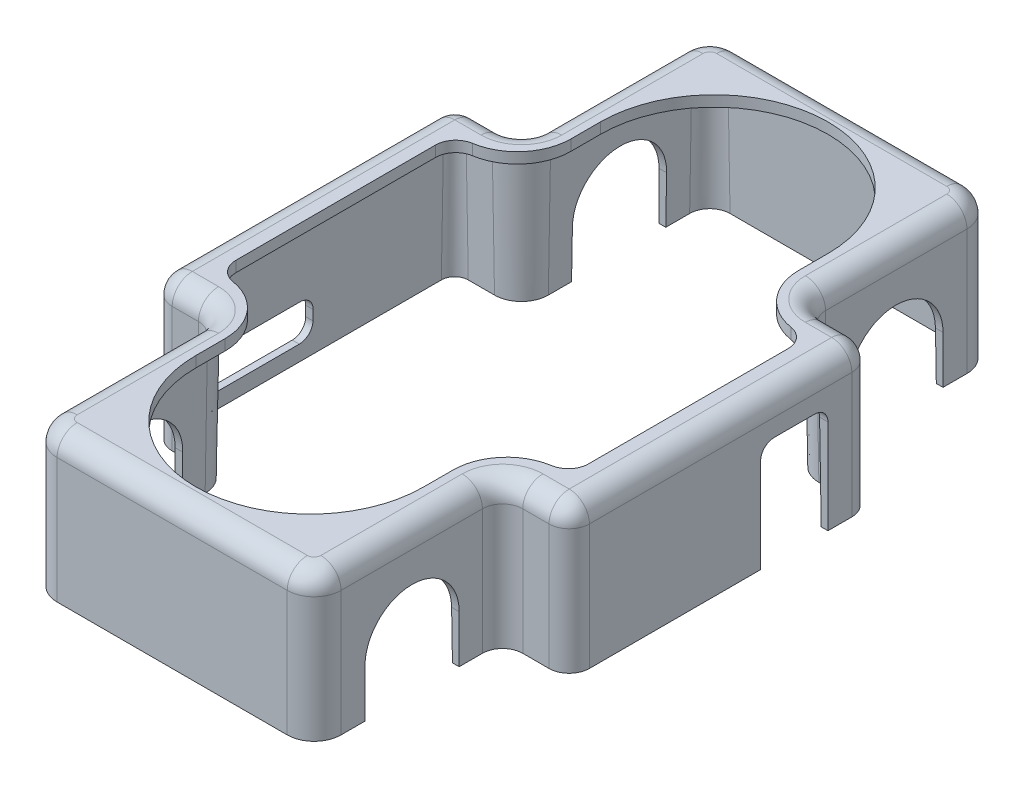
SolidWorks part; units mm, degrees
ref_plane "Front Plane" through (0, 0, 0) normal (0, 0, 1) x (1, 0, 0)
ref_plane "Top Plane" through (0, 0, 0) normal (0, 1, 0) x (1, 0, 0)
ref_plane "Right Plane" through (0, 0, 0) normal (1, 0, 0) x (0, 0, -1)
sketch "Sketch1" plane through (0, 0, 0) normal (0, 1, 0) x (1, 0, 0)
  line L1 (-155, -252.5) -> (155, -252.5)
  line L2 (-155, -252.5) -> (-155, 252.5)
  line L3 (-155, 252.5) -> (155, 252.5)
  line L4 (155, -252.5) -> (155, 252.5)
  line L5 (-155, -252.5) -> (155, 252.5) construction
  line L6 (-155, 252.5) -> (155, -252.5) construction
  point P0 (0, 0)
  dimension "D1" = 310
  dimension "D2" = 505
extrude "Boss-Extrude1" add sketch "Sketch1" along normal blind 108
sketch "Sketch2" plane through (0, 0, 0) normal (0, -1, 0) x (-1, 0, 0)
  line L0 (155, -252.5) -> (-155, -252.5) construction
  line L1 (180.5, -252.5) -> (105.5, -252.5)
  line L2 (180.5, -252.5) -> (180.5, -112.5)
  line L3 (180.5, -112.5) -> (105.5, -112.5)
  line L4 (105.5, -252.5) -> (105.5, -112.5)
  line L5 (0, 0) -> (-155, 0) construction
  line L6 (-155, -252.5) -> (-155, 252.5) construction
  line L7 (0, 0) -> (0, -252.5) construction
  line L8 (-105.5, -252.5) -> (-105.5, -112.5)
  line L9 (-180.5, -112.5) -> (-105.5, -112.5)
  line L10 (-180.5, -252.5) -> (-180.5, -112.5)
  line L11 (-180.5, -252.5) -> (-105.5, -252.5)
  line L12 (-180.5, 252.5) -> (-105.5, 252.5)
  line L13 (-180.5, 252.5) -> (-180.5, 112.5)
  line L14 (-180.5, 112.5) -> (-105.5, 112.5)
  line L15 (-105.5, 252.5) -> (-105.5, 112.5)
  line L16 (105.5, 252.5) -> (105.5, 112.5)
  line L17 (180.5, 112.5) -> (105.5, 112.5)
  line L18 (180.5, 252.5) -> (180.5, 112.5)
  line L19 (180.5, 252.5) -> (105.5, 252.5)
  dimension "D1" = 140
  dimension "D2" = 75
extrude "Cut-Extrude1" cut sketch "Sketch2" against normal through all
fillet "Fillet1" radius 15 4 edges at (105.5, 54, 112.5) (-105.5, 54, 112.5) (105.5, 54, -112.5) (-105.5, 54, -112.5)
fillet "Fillet3" radius 20 4 edges at (105.5, 54, 252.5) (-105.5, 54, 252.5) (105.5, 54, -252.5) (-105.5, 54, -252.5)
fillet "Fillet4" radius 15 20 edges at (-109.8934, 108, 116.8934) (-105.5, 108, 180) (-99.6421, 108, 246.6421) (0, 108, 252.5) (99.6421, 108, 246.6421) (109.8934, 108, 116.8934) (-109.8934, 108, -116.8934) (-105.5, 108, -180) (-99.6421, 108, -246.6421) (0, 108, -252.5) (99.6421, 108, -246.6421) (105.5, 108, -180) (109.8934, 108, -116.8934) (105.5, 108, 180) (155, 108, 0) (-155, 108, 0) (-137.75, 108, 112.5) (137.75, 108, 112.5) (-137.75, 108, -112.5) (137.75, 108, -112.5)
fillet "Fillet5" radius 15 8 edges at (-150.6066, 103.6066, 108.1066) (-150.6066, 103.6066, -108.1066) (150.6066, 103.6066, -108.1066) (150.6066, 103.6066, 108.1066) (-155, 46.5, 112.5) (-155, 46.5, -112.5) (155, 46.5, -112.5) (155, 46.5, 112.5)
ref_plane "Plane1" through (0, -10, 0) normal (0, -1, 0) x (-1, 0, 0)
sketch "Sketch16" plane through (-105.5, 0, 0) normal (-1, 0, 0) x (0, 0, 1)
  line L0 (-179.75, 35.4494) -> (-179.75, -45.4494) construction
  line L1 (-144.75, 35.4494) -> (-144.75, -45.4494)
  line L2 (-214.75, 35.4494) -> (-214.75, -45.4494)
  line L3 (0, 0) -> (0, -82.7143) construction
  line L4 (179.75, 35.4494) -> (179.75, -45.4494) construction
  line L5 (144.75, 35.4494) -> (144.75, -45.4494)
  line L6 (214.75, 35.4494) -> (214.75, -45.4494)
  line L7 (-232.5, 0) -> (-127.5, 0) construction
  arc A0 (-144.75, 35.4494) -> (-214.75, 35.4494) centre (-179.75, 35.4494) ccw
  arc A1 (-214.75, -45.4494) -> (-144.75, -45.4494) centre (-179.75, -45.4494) ccw
  arc A2 (144.75, 35.4494) -> (214.75, 35.4494) centre (179.75, 35.4494) cw
  arc A3 (214.75, -45.4494) -> (144.75, -45.4494) centre (179.75, -45.4494) cw
  point P2 (-179.75, -5)
  point P11 (179.75, -5)
  dimension "D1" = 35
  dimension "D2" = 5
extrude "Cut-Extrude2" cut sketch "Sketch16" against normal through all
sketch "Sketch17" plane through (0, 0, 0) normal (0, -1, 0) x (-1, 0, 0)
  line L413 (-100.5, -214.75) -> (-100.5, -232.5)
  line L414 (-100.5, -144.75) -> (-100.5, -214.75)
  line L415 (-100.5, -127.5) -> (-100.5, -144.75)
  line L416 (-140, -107.5) -> (-120.5, -107.5)
  line L417 (-150, 97.5) -> (-150, -97.5)
  line L418 (-120.5, 107.5) -> (-140, 107.5)
  line L419 (-100.5, 144.75) -> (-100.5, 127.5)
  line L420 (-100.5, 214.75) -> (-100.5, 144.75)
  line L421 (-100.5, 232.5) -> (-100.5, 214.75)
  line L422 (85.5, 247.5) -> (-85.5, 247.5)
  line L423 (100.5, 214.75) -> (100.5, 232.5)
  line L424 (100.5, 144.75) -> (100.5, 214.75)
  line L425 (100.5, 127.5) -> (100.5, 144.75)
  line L426 (140, 107.5) -> (120.5, 107.5)
  line L427 (150, -97.5) -> (150, 97.5)
  line L428 (120.5, -107.5) -> (140, -107.5)
  line L429 (100.5, -144.75) -> (100.5, -127.5)
  line L430 (100.5, -214.75) -> (100.5, -144.75)
  line L431 (100.5, -232.5) -> (100.5, -214.75)
  line L432 (-85.5, -247.5) -> (85.5, -247.5)
  line L433 (-100.5, -214.75) -> (-100.5, -232.5)
  line L434 (-100.5, -144.75) -> (-100.5, -214.75)
  line L435 (-100.5, -127.5) -> (-100.5, -144.75)
  line L436 (-140, -107.5) -> (-120.5, -107.5)
  line L437 (-150, 97.5) -> (-150, -97.5)
  line L438 (-120.5, 107.5) -> (-140, 107.5)
  line L439 (-100.5, 144.75) -> (-100.5, 127.5)
  line L440 (-100.5, 214.75) -> (-100.5, 144.75)
  line L441 (-100.5, 232.5) -> (-100.5, 214.75)
  line L442 (85.5, 247.5) -> (-85.5, 247.5)
  line L443 (100.5, 214.75) -> (100.5, 232.5)
  line L444 (100.5, 144.75) -> (100.5, 214.75)
  line L445 (100.5, 127.5) -> (100.5, 144.75)
  line L446 (140, 107.5) -> (120.5, 107.5)
  line L447 (150, -97.5) -> (150, 97.5)
  line L448 (120.5, -107.5) -> (140, -107.5)
  line L449 (100.5, -144.75) -> (100.5, -127.5)
  line L450 (100.5, -214.75) -> (100.5, -144.75)
  line L451 (100.5, -232.5) -> (100.5, -214.75)
  line L452 (-85.5, -247.5) -> (85.5, -247.5)
  arc A235 (-100.5, -232.5) -> (-85.5, -247.5) centre (-85.5, -232.5) ccw
  arc A236 (-100.5, -127.5) -> (-120.5, -107.5) centre (-120.5, -127.5) ccw
  arc A237 (-150, -97.5) -> (-140, -107.5) centre (-140, -97.5) ccw
  arc A238 (-140, 107.5) -> (-150, 97.5) centre (-140, 97.5) ccw
  arc A239 (-120.5, 107.5) -> (-100.5, 127.5) centre (-120.5, 127.5) ccw
  arc A240 (-85.5, 247.5) -> (-100.5, 232.5) centre (-85.5, 232.5) ccw
  arc A241 (100.5, 232.5) -> (85.5, 247.5) centre (85.5, 232.5) ccw
  arc A242 (100.5, 127.5) -> (120.5, 107.5) centre (120.5, 127.5) ccw
  arc A243 (150, 97.5) -> (140, 107.5) centre (140, 97.5) ccw
  arc A244 (140, -107.5) -> (150, -97.5) centre (140, -97.5) ccw
  arc A245 (120.5, -107.5) -> (100.5, -127.5) centre (120.5, -127.5) ccw
  arc A246 (85.5, -247.5) -> (100.5, -232.5) centre (85.5, -232.5) ccw
  arc A247 (-100.5, -232.5) -> (-85.5, -247.5) centre (-85.5, -232.5) ccw
  arc A248 (-100.5, -127.5) -> (-120.5, -107.5) centre (-120.5, -127.5) ccw
  arc A249 (-150, -97.5) -> (-140, -107.5) centre (-140, -97.5) ccw
  arc A250 (-140, 107.5) -> (-150, 97.5) centre (-140, 97.5) ccw
  arc A251 (-120.5, 107.5) -> (-100.5, 127.5) centre (-120.5, 127.5) ccw
  arc A252 (-85.5, 247.5) -> (-100.5, 232.5) centre (-85.5, 232.5) ccw
  arc A253 (100.5, 232.5) -> (85.5, 247.5) centre (85.5, 232.5) ccw
  arc A254 (100.5, 127.5) -> (120.5, 107.5) centre (120.5, 127.5) ccw
  arc A255 (150, 97.5) -> (140, 107.5) centre (140, 97.5) ccw
  arc A256 (140, -107.5) -> (150, -97.5) centre (140, -97.5) ccw
  arc A257 (120.5, -107.5) -> (100.5, -127.5) centre (120.5, -127.5) ccw
  arc A258 (85.5, -247.5) -> (100.5, -232.5) centre (85.5, -232.5) ccw
  dimension "D1" = 5
extrude "Cut-Extrude3" cut sketch "Sketch17" against normal blind 100 draft 1
sketch "Sketch18" plane through (-155, 0, 0) normal (-1, 0, 0) x (0, 0, 1)
  line L1 (-1.75, 39.0885) -> (85.25, 39.0885)
  line L2 (-1.75, 39.0885) -> (-1.75, 11.7)
  line L3 (-1.75, 11.7) -> (85.25, 11.7)
  line L4 (85.25, 39.0885) -> (85.25, 11.7)
extrude "Cut-Extrude4" cut sketch "Sketch18" against normal blind 90
fillet "Fillet6" radius 10 4 edges at (-152.1589, 39.0885, 85.25) (-152.3979, 11.7, 85.25) (-152.3979, 11.7, -1.75) (-152.1589, 39.0885, -1.75)
sketch "Sketch19" plane through (155, 0, 0) normal (1, 0, 0) x (0, 0, -1)
  line L1 (29.75, 80) -> (79.75, 80)
  line L2 (29.75, 80) -> (29.75, -18.3945)
  line L3 (29.75, -18.3945) -> (79.75, -18.3945)
  line L4 (79.75, 80) -> (79.75, -18.3945)
extrude "Cut-Extrude5" cut sketch "Sketch19" against normal blind 90
fillet "Fillet7" radius 10 2 edges at (151.8018, 80, -29.75) (151.8018, 80, -79.75)
sketch "Sketch20" plane through (0, 108, 0) normal (0, 1, 0) x (1, 0, 0)
  line L0 (0, 234.8657) -> (0, -234.8657)
  line L6 (-131, -88.5) -> (-120.5, -88.5)
  line L8 (0, 0) -> (-131, 0) construction
  line L9 (-84.6157, -150.25) -> (-84.6157, -112.2253)
  line L10 (84.6157, 150.25) -> (84.6157, 112.2253)
  line L11 (-131, 88.5) -> (-120.5, 88.5)
  line L12 (-120.5, -88.5) -> (-131, -88.5)
  line L13 (-131, -88.5) -> (-131, 88.5)
  line L14 (-131, 88.5) -> (-120.5, 88.5)
  line L16 (-131, -88.5) -> (-131, 88.5)
  line L17 (-131, 88.5) -> (-120.5, 88.5)
  line L18 (131, 88.5) -> (120.5, 88.5)
  line L19 (0, -234.8657) -> (0, 237.5)
  line L20 (131, -88.5) -> (131, 88.5)
  line L21 (131, 88.5) -> (120.5, 88.5)
  line L22 (84.6157, -150.25) -> (84.6157, -112.2253)
  line L23 (131, -88.5) -> (120.5, -88.5)
  line L27 (-84.6157, 150.25) -> (-84.6157, 112.2253)
  arc A6 (-84.6157, 150.25) -> (84.6157, 150.25) centre (0, 150.25) cw
  arc A8 (-120.5, -88.5) -> (-84.6157, -112.2253) centre (-120.5, -127.5) cw
  arc A9 (-84.6157, -150.25) -> (84.6157, -150.25) centre (0, -150.25) ccw
  arc A10 (-84.6157, 150.25) -> (0, 234.8657) centre (0, 150.25) cw
  arc A11 (-81.5, -127.5) -> (-120.5, -88.5) centre (-120.5, -127.5) ccw
  arc A12 (-120.5, 88.5) -> (-81.5, 127.5) centre (-120.5, 127.5) ccw
  arc A16 (120.5, 88.5) -> (84.6157, 112.2253) centre (120.5, 127.5) cw
  arc A17 (120.5, -88.5) -> (84.6157, -112.2253) centre (120.5, -127.5) ccw
  arc A24 (-120.5, 88.5) -> (-81.5, 127.5) centre (-120.5, 127.5) ccw
  arc A25 (-120.5, 88.5) -> (-84.6157, 112.2253) centre (-120.5, 127.5) ccw
  point P25 (0, 0)
  dimension "D1" = 9
  dimension "D3" = 9
extrude "Cut-Extrude7" cut sketch "Sketch20" against normal blind 90
fillet "Fillet12" radius 40 4 edges at (-84.6157, 104, 112.2253) (84.6157, 104, 112.2253) (84.6157, 104, -112.2253) (-84.6157, 104, -112.2253)
fillet "Fillet13" radius 15 4 edges at (-131, 104, 88.5) (131, 104, -88.5) (131, 104, 88.5) (-131, 104, -88.5)
